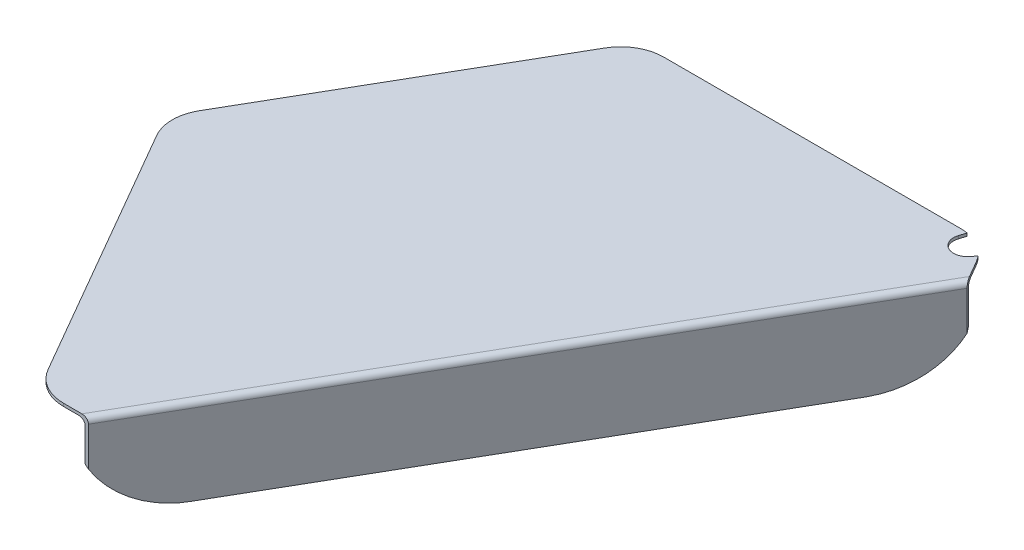
SolidWorks part; units mm, degrees
ref_plane "Alzado" through (0, 0, 0) normal (0, 0, 1) x (1, 0, 0)
ref_plane "Planta" through (0, 0, 0) normal (0, 1, 0) x (1, 0, 0)
ref_plane "Vista lateral" through (0, 0, 0) normal (1, 0, 0) x (0, 0, -1)
sketch "Croquis1" plane through (0, 0, 0) normal (0, 1, 0) x (1, 0, 0)
  line L0 (-63.1182, -98.8234) -> (-115.0797, -8.8234)
  line L1 (-115.0797, 6.1766) -> (-63.1182, 96.1766)
  line L2 (-50.1278, 103.6766) -> (53.7952, 103.6766)
  line L3 (71.1157, 88.6766) -> (66.7856, 96.1766)
  line L4 (-41.4676, -106.3234) -> (-50.1278, -106.3234)
  line L5 (103.3607, 144.5264) -> (-41.4676, -106.3234)
  line L11 (56.3411, 103.4023) -> (55.6093, 101.1316)
  line L12 (63.9317, 96.7848) -> (65.2083, 98.3295)
  line L13 (56.3584, 103.456) -> (55.6093, 101.1316)
  line L14 (63.9317, 96.7848) -> (65.2421, 98.3704)
  arc A0 (-115.0797, 6.1766) -> (-115.0797, -8.8234) centre (-102.0893, -1.3234) ccw
  arc A1 (-50.1278, 103.6766) -> (-63.1182, 96.1766) centre (-50.1278, 88.6766) ccw
  arc A2 (66.7856, 96.1766) -> (65.2421, 98.3704) centre (53.7952, 88.6766) ccw
  arc A3 (-63.1182, -98.8234) -> (-50.1278, -106.3234) centre (-50.1278, -91.3234) ccw
  arc A4 (56.3584, 103.456) -> (53.7952, 103.6766) centre (53.7952, 88.6766) ccw
  arc A8 (55.6093, 101.1316) -> (63.9317, 96.7848) centre (60.1426, 99.6706) ccw
  arc A9 (55.6093, 101.1316) -> (63.9317, 96.7848) centre (60.1426, 99.6706) ccw
  dimension "D1" = 103.923
  dimension "D2" = 103.923
  dimension "D3" = 103.923
  dimension "D4" = 120
  dimension "D5" = 0.1
extrude "Saliente-Extruir1" add sketch "Croquis1" along normal blind 1 contours L0 A3 L4 L5 L3 A2 L2 A1 L1 A0 region at (-31.5151, 0, -17.5988)
sketch "Croquis2" plane through (0, 0, 0) normal (0, -1, 0) x (1, 0, 0)
  line L0 (71.1157, -88.6766) -> (-41.4676, 106.3234) construction
  line L1 (71.1157, -88.6766) -> (-41.4676, 106.3234)
  line L3 (-41.4676, 106.3234) -> (-50.1278, 106.3234) construction
  line L4 (71.1157, -88.6766) -> (66.7856, -96.1766) construction
  line L5 (71.1157, -88.6766) -> (70.5384, -89.6766)
  line L6 (-42.6223, 106.3234) -> (70.5384, -89.6766)
  line L7 (-41.4676, 106.3234) -> (-42.6223, 106.3234)
  line L8 (71.1157, -88.6766) -> (70.5384, -89.6766)
  line M19 (66.7856, -96.1766) -> (71.1157, -88.6766)
  line M20 (71.1157, -88.6766) -> (-41.4676, 106.3234)
  line M21 (-41.4676, 106.3234) -> (-50.1278, 106.3234)
  dimension "D1" = 1
extrude "Saliente-Extruir2" add sketch "Croquis2" along normal blind 31 contours L6 M21 M19 M20 region at (14.3907, 0, 8.5732)
fillet "Redondeo1" radius 2 2 edges at (14.8241, 1, 8.8234) (13.9581, 0, 8.3234)
sketch "Croquis3" plane through (14.9387, 0, 8.6249) normal (0.866, 0, 0.5) x (0.5, 0, -0.866)
  line L13 (-117.1427, 0.8) -> (-128.5092, -12.943)
  line L15 (-65.1811, 0.8) -> (-117.1427, 0.8)
  line L16 (-78.0456, -29.2) -> (-43.5305, -29.2)
  line L19 (116.6842, 0.8) -> (140.2294, -2.7085)
  line L20 (116.6842, 0.8) -> (100.6842, 0.8)
  line L21 (100.6842, 0.8) -> (64.7227, 0.8)
  line L22 (116.6842, 0.8) -> (100.6842, 0.8)
  line L26 (78.3796, -29.2) -> (86.3733, -29.2)
  line L34 (86.3733, -29.2) -> (-78.0456, -29.2)
  line L35 (140.2294, -2.7085) -> (121.2929, -43.8284)
  line L36 (121.2929, -43.8284) -> (-113.2262, -43.8284)
  line L37 (-113.2262, -43.8284) -> (-128.5092, -12.943)
  line L118 (-78.7959, -29.2) -> (-78.0456, -29.2)
  line L119 (-78.7959, -29.2) -> (-78.0456, -29.2)
  line L120 (-86.8318, -29.2) -> (-78.7959, -29.2)
  line L121 (-86.8318, -29.2) -> (-78.7959, -29.2)
  line L123 (77.6288, -29.2) -> (78.3796, -29.2)
  line L124 (77.6288, -29.2) -> (78.3796, -29.2)
  line L125 (43.072, -29.2) -> (77.6288, -29.2)
  line L126 (43.072, -29.2) -> (77.6288, -29.2)
  ellipse E2 centre (-86.8318, 0.8) end of major axis (-56.5209, 0.8) minor radius 30 (-117.1427, 0.8) -> (-86.8318, -29.2) ccw
  ellipse E3 centre (-43.5305, 0.8) end of major axis (-43.5305, 30.8) minor radius 21.6506 (-65.1811, 0.8) -> (-43.5305, -29.2) ccw
  ellipse E4 centre (-86.8318, 0.8) end of major axis (-56.5209, 0.8) minor radius 30 (-117.1427, 0.8) -> (-86.8318, -29.2) ccw
  ellipse E5 centre (43.072, 0.8) end of major axis (43.072, -29.2) minor radius 21.6506 (43.072, -29.2) -> (64.7227, 0.8) ccw
  ellipse E9 centre (86.3733, 0.8) end of major axis (56.0624, 0.8) minor radius 30 (86.3733, -29.2) -> (116.6842, 0.8) ccw
  ellipse E14 centre (86.3733, 0.8) end of major axis (56.0624, 0.8) minor radius 30 (86.3733, -29.2) -> (116.6842, 0.8) ccw
  dimension "D3" = 0
  dimension "D4" = 0
extrude "Cortar-Extruir1" cut sketch "Croquis3" against normal blind 2 contours E14 L34 L119 L121 E4 | E14 E4 L13 L37 L36 L35 L19 region at (20.6764, -31.8433, -1.3131)
